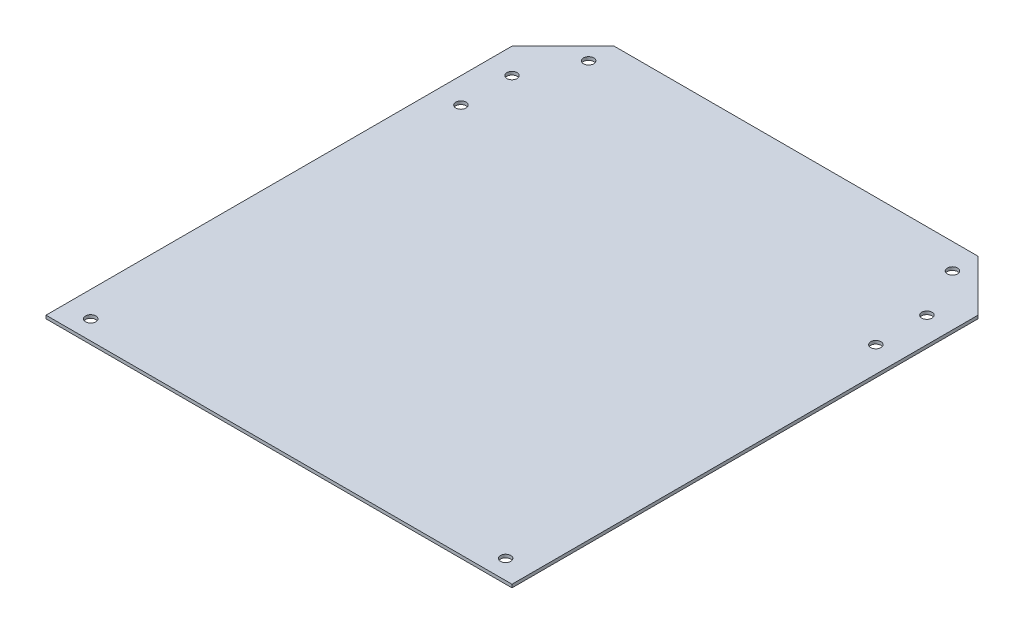
SolidWorks part; units mm, degrees
ref_plane "Front Plane" through (0, 0, 0) normal (0, 0, 1) x (1, 0, 0)
ref_plane "Top Plane" through (0, 0, 0) normal (0, 1, 0) x (1, 0, 0)
ref_plane "Right Plane" through (0, 0, 0) normal (1, 0, 0) x (0, 0, -1)
sketch "Sketch3" plane through (0, 0, 0) normal (0, 1, 0) x (1, 0, 0)
  line L1 (-96.1565, 9.0785) -> (135.6185, 9.0785)
  line L2 (-96.1565, 9.0785) -> (-96.1565, 240.8535)
  line L6 (135.6185, 9.0785) -> (135.6185, 240.8535)
  line L7 (110.2185, 266.2535) -> (-70.7565, 266.2535)
  line L12 (-96.1565, 240.8535) -> (-70.7565, 266.2535)
  line L13 (135.6185, 240.8535) -> (110.2185, 266.2535)
extrude "Boss-Extrude1" add sketch "Sketch3" along normal blind 1.5875
hole_wizard "#10 Clearance Hole1" positions "Sketch11" profile "Sketch12" hole size "#10" standard "ANSI Inch" end condition through all
sketch "Sketch11" plane through (0, 1.5875, 0) normal (0, 1, 0) x (1, 0, 0)
  point P0 (-83.4565, -25.8465)
  point P3 (-83.4565, 202.7535)
  point P6 (-83.4565, 228.1535)
  point P9 (-70.7565, 253.5535)
  point P12 (122.9185, 202.7535)
  point P15 (122.9185, 228.1535)
  point P18 (110.2185, 253.5535)
  point P21 (-83.4565, 18.6035)
  point P24 (122.9185, 18.6035)
sketch "Sketch12" plane through (-83.4565, 1.5875, 25.8465) normal (1, 0, 0) x (0, 0, 1)
  line L0 (0, 0) -> (0, 1.5875)
  line L1 (0, 1.5875) -> (2.5527, 1.5875)
  line L2 (2.5527, 1.5875) -> (2.5527, 0)
  line L5 (2.5527, 0) -> (0, 0)
  line L11 (0, -6.35) -> (0, 107.95) construction
  dimension "Thru Hole Dia." = 5.1054
  dimension "Thru Hole Depth" = 1.5875
